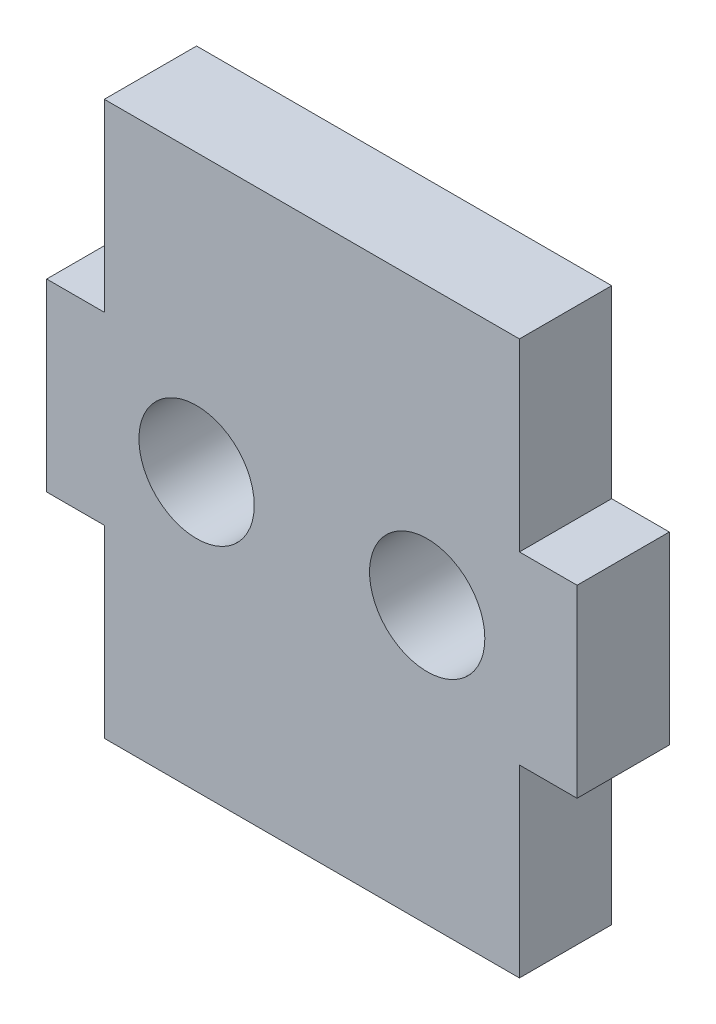
SolidWorks part; units mm, degrees
ref_plane "Front Plane" through (0, 0, 0) normal (0, 0, 1) x (1, 0, 0)
ref_plane "Top Plane" through (0, 0, 0) normal (0, 1, 0) x (1, 0, 0)
ref_plane "Right Plane" through (0, 0, 0) normal (1, 0, 0) x (0, 0, -1)
sketch "Model" plane through (0, 0, 0) normal (0, 0, 1) x (1, 0, 0)
  line L37 (1952.1768, 1458.8841) -> (1950.9268, 1458.8841)
  line L38 (1961.1768, 1458.8841) -> (1962.4268, 1458.8841)
  line L39 (1952.1768, 1454.8841) -> (1961.1768, 1454.8841)
  line L40 (1952.1768, 1458.8841) -> (1952.1768, 1454.8841)
  line L41 (1961.1768, 1458.8841) -> (1961.1768, 1454.8841)
  line L126 (1961.1768, 1462.8841) -> (1962.4268, 1462.8841)
  line L127 (1952.1768, 1462.8841) -> (1950.9268, 1462.8841)
  line L128 (1961.1768, 1466.8841) -> (1952.1768, 1466.8841)
  line L129 (1961.1768, 1462.8841) -> (1961.1768, 1466.8841)
  line L130 (1952.1768, 1462.8841) -> (1952.1768, 1466.8841)
  line L131 (1950.9268, 1462.8841) -> (1950.9268, 1458.8841)
  line L132 (1962.4268, 1462.8841) -> (1962.4268, 1458.8841)
  circle A81 centre (1959.1768, 1460.8841) radius 1.25
  circle A82 centre (1954.1768, 1460.8841) radius 1.25
extrude "Boss-Extrude1" add sketch "Model" along normal blind 2
